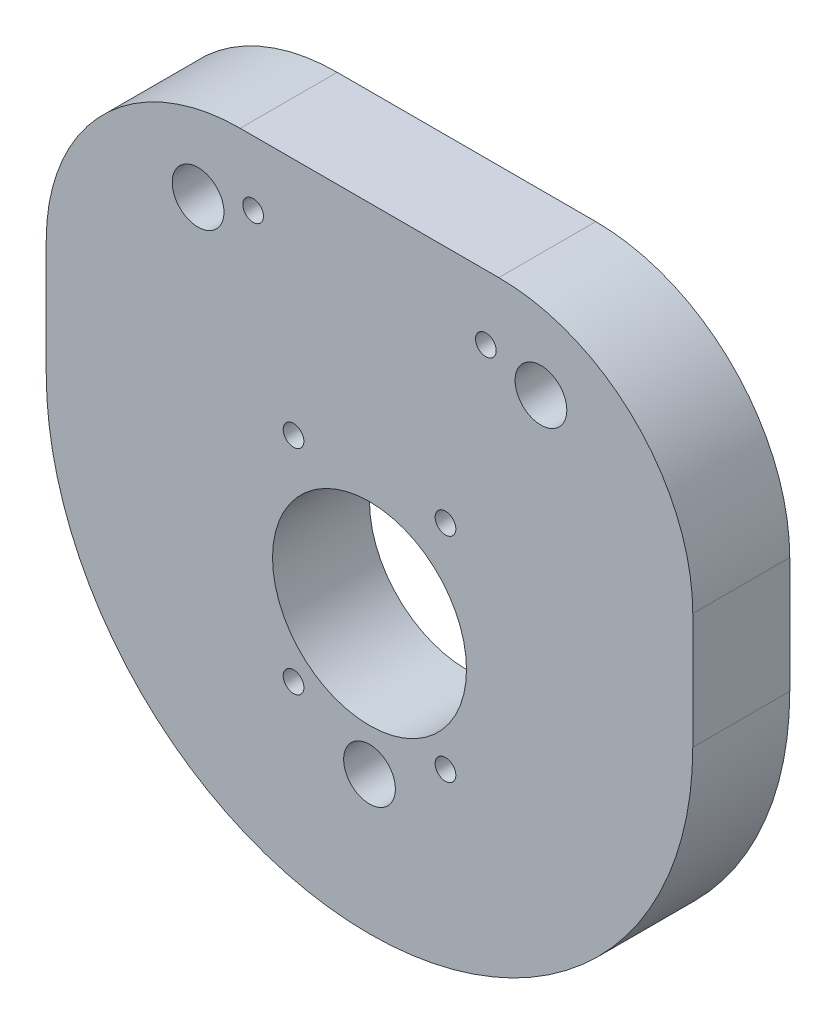
SolidWorks part; units mm, degrees
ref_plane "Front Plane" through (0, 0, 0) normal (0, 0, 1) x (1, 0, 0)
ref_plane "Top Plane" through (0, 0, 0) normal (0, 1, 0) x (1, 0, 0)
ref_plane "Right Plane" through (0, 0, 0) normal (1, 0, 0) x (0, 0, -1)
sketch "Sketch1" plane through (0, 0, 0) normal (0, 0, 1) x (1, 0, 0)
  line L0 (4, 20) -> (-4, 20) construction
  line L1 (-50, 20) -> (50, 20)
  line L2 (-50, 20) -> (-50, -77.9165)
  line L3 (-50, -77.9165) -> (50, -77.9165)
  line L4 (50, 20) -> (50, -77.9165)
  circle A0 centre (18, 10) radius 1.6
  circle A1 centre (-18, 10) radius 1.6
  circle A2 centre (-11.75, -17) radius 1.6
  circle A3 centre (11.75, -17) radius 1.6
  circle A4 centre (11.75, -50) radius 1.6
  circle A5 centre (-11.75, -50) radius 1.6
  point P6 (0, -77.9165)
  dimension "D2" = 3.2
  dimension "D1" = 100
extrude "Boss-Extrude1" add sketch "Sketch1" along normal blind 15
sketch "Sketch2" plane through (0, 0, 15) normal (0, 0, 1) x (1, 0, 0)
  circle A0 centre (-26.5165, 7.5) radius 4
  circle A1 centre (26.5165, 7.5) radius 4
  circle A2 centre (0, -56.5165) radius 4
  dimension "D1" = 8
extrude "Cut-Extrude1" cut sketch "Sketch2" against normal offset from surface (12 mm away) 3 up to face at (0, -28.9582, 0)
fillet "Fillet1" radius 50 2 edges at (-50, -77.9165, 7.5) (50, -77.9165, 7.5)
fillet "Fillet2" radius 30 2 edges at (-50, 20, 7.5) (50, 20, 7.5)
sketch "Sketch3" plane through (0, 0, 0) normal (0, 0, -1) x (-1, 0, 0)
  circle A0 centre (0, -35) radius 15
  dimension "D2" = 30
  dimension "D1" = 35
extrude "Cut-Extrude2" cut sketch "Sketch3" against normal through all both and the other way through all
